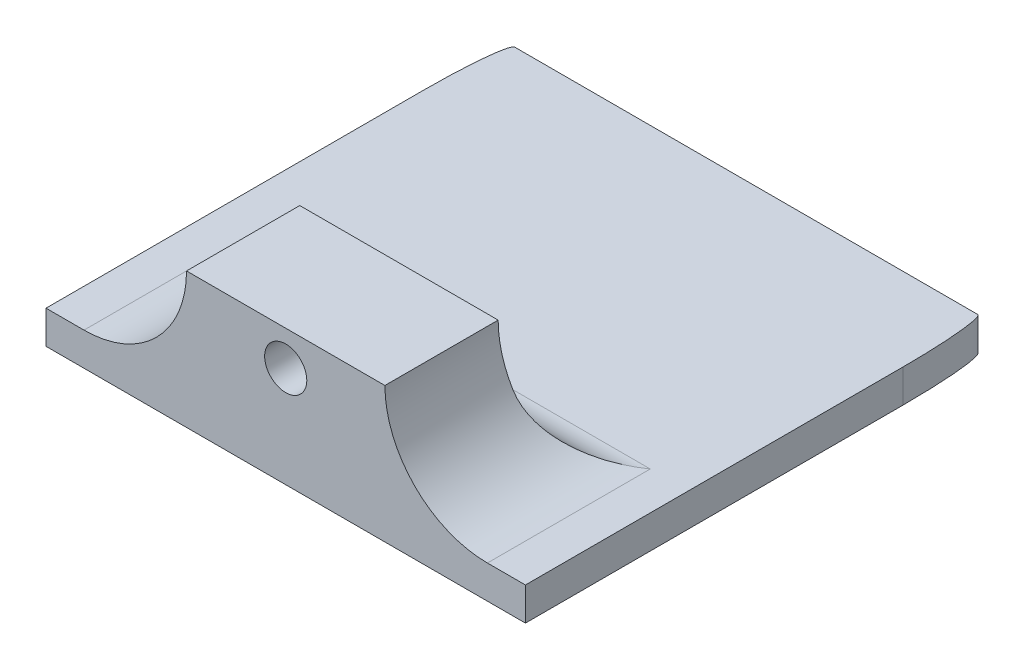
SolidWorks part; units mm, degrees
material "7050-T7651"
ref_plane "Front Plane" through (0, 0, 0) normal (0, 0, 1) x (1, 0, 0)
ref_plane "Top Plane" through (0, 0, 0) normal (0, 1, 0) x (1, 0, 0)
ref_plane "Right Plane" through (0, 0, 0) normal (1, 0, 0) x (0, 0, -1)
sketch "Sketch2" plane through (0, 0, 0) normal (0, 0, 1) x (1, 0, 0)
  line L1 (-29, -12.2) -> (29, -12.2)
  line L2 (-29, -12.2) -> (-29, 4.2)
  line L3 (-29, 4.2) -> (29, 4.2)
  line L4 (29, -12.2) -> (29, 4.2)
  circle A0 centre (0, 0) radius 2.55
  point P7 (0, 4.2)
  dimension "D1" = 5.1
  dimension "D2" = 4.2
  dimension "D3" = 58
  dimension "D4" = 12.2
extrude "Boss-Extrude1" add sketch "Sketch2" against normal blind 12.2
cosmetic thread "Cosmetic Thread1" parameters "D1"=10, "D2"=6
sketch "Sketch3" plane through (0, 0, -12.2) normal (0, 0, -1) x (-1, 0, 0)
  line L1 (-29, -12.2) -> (29, -12.2)
  line L2 (-29, -12.2) -> (-29, 4.2)
  line L3 (-29, 4.2) -> (29, 4.2)
  line L4 (29, -12.2) -> (29, 4.2)
extrude "Boss-Extrude2" add sketch "Sketch3" along normal blind 1.5
sketch "Sketch4" plane through (0, 0, -13.7) normal (0, 0, -1) x (-1, 0, 0)
  line L0 (29, -12.2) -> (29, 4.2) construction
  line L1 (-29, -12.2) -> (29, -12.2)
  line L2 (-29, -12.2) -> (-29, -8.2)
  line L3 (-29, -8.2) -> (29, -8.2)
  line L4 (29, -12.2) -> (29, -8.2)
  dimension "D1" = 4
extrude "Boss-Extrude3" add sketch "Sketch4" along normal blind 42
fillet "Fillet1" radius 10 1 edges at (29, -10.2, -55.7) second distance 1 first distance on face at (29, -5.4, -23.1333)
fillet "Fillet2" radius 10 1 edges at (-29, -10.2, -55.7) second distance 1 first distance on face at (-29, -5.4, -23.1333)
fillet "Fillet3" radius 6 1 edges at (0, -8.2, -13.7)
sketch "Sketch5" plane through (0, 0, 0) normal (0, 0, 1) x (1, 0, 0)
  line L0 (0, 0) -> (0, 9.4705) construction
  line L8 (29, 4.2) -> (12, 4.2)
  line L11 (29, -12.2) -> (29, 4.2) construction
  line L12 (29, 4.2) -> (-29, 4.2) construction
  line L13 (12, -1.0562) -> (12, 7.9794) construction
  line L14 (24.4, -8.2) -> (29, -8.2)
  line L15 (29, -8.2) -> (29, 4.2)
  line L16 (-24.4, -8.2) -> (-29, -8.2)
  line L17 (-29, 4.2) -> (-12, 4.2)
  line L18 (-29, -8.2) -> (-29, 4.2)
  line L19 (-28, -8.2) -> (28, -8.2) construction
  arc A0 (12, 4.2) -> (24.4, -8.2) centre (24.4, 4.2) ccw
  arc A1 (-12, 4.2) -> (-24.4, -8.2) centre (-24.4, 4.2) cw
  point P20 (25.4995, -8.2)
  dimension "D1" = 17
extrude "Cut-Extrude1" cut sketch "Sketch5" against normal up to next
